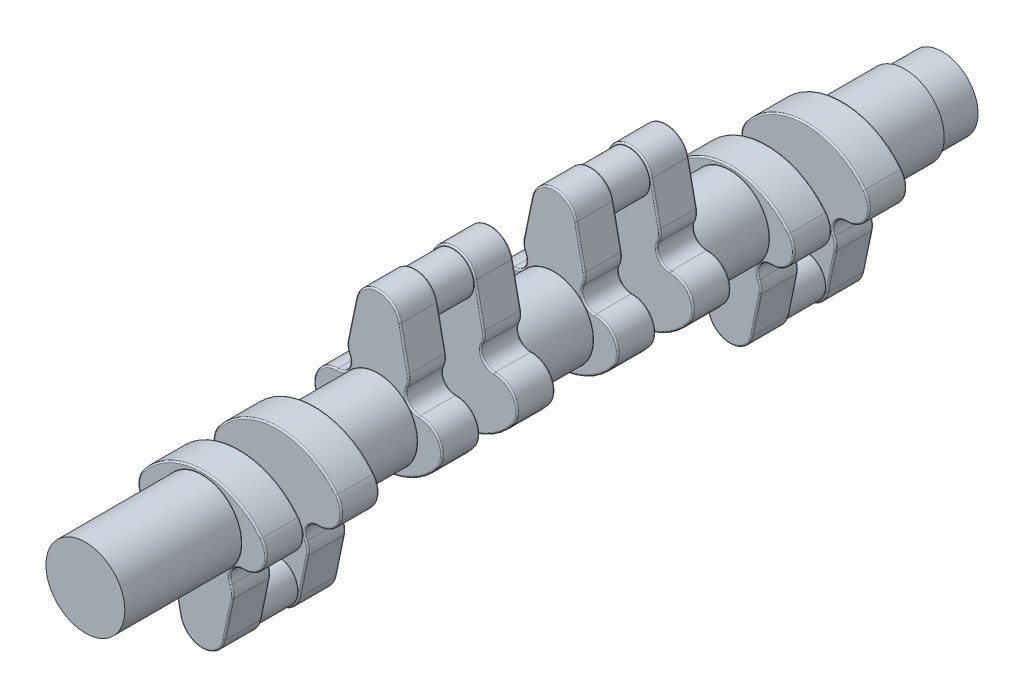
SolidWorks part; units mm, degrees
ref_plane "Front Plane" through (0, 0, 0) normal (0, 0, 1) x (1, 0, 0)
ref_plane "Top Plane" through (0, 0, 0) normal (0, 1, 0) x (1, 0, 0)
ref_plane "Right Plane" through (0, 0, 0) normal (1, 0, 0) x (0, 0, -1)
sketch "Sketch1" plane through (0, 0, 0) normal (0, 0, 1) x (1, 0, 0)
  line L0 (0, 32.598) -> (0, -43.8439) construction
  line L1 (-17.034, 1.0662) -> (-11.7495, -24.3911)
  line L2 (17.034, 1.0662) -> (11.7495, -24.3911)
  arc A0 (31.5175, 32.6781) -> (-31.5175, 32.6781) centre (0, 8.0479) ccw
  arc A1 (-31.5175, 32.6781) -> (-21.8275, 13.2913) centre (-22.0622, 25.289) ccw
  arc A2 (31.5175, 32.6781) -> (21.8275, 13.2913) centre (22.0622, 25.289) cw
  arc A3 (-21.8275, 13.2913) -> (-17.034, 1.0662) centre (-21.6906, 6.2927) cw
  arc A4 (21.8275, 13.2913) -> (17.034, 1.0662) centre (21.6906, 6.2927) ccw
  arc A5 (-11.7495, -24.3911) -> (0, -33.9521) centre (0, -21.9521) ccw
  arc A6 (11.7495, -24.3911) -> (0, -33.9521) centre (0, -21.9521) cw
  point P20 (0, 48.0479)
  dimension "D1" = 40
  dimension "D2" = 12
  dimension "D3" = 7
  dimension "D5" = 12
  dimension "D4" = 26
  dimension "D6" = 82
extrude "Boss-Extrude1" add sketch "Sketch1" along normal blind 20
sketch "Sketch2" plane through (0, 0, 0) normal (0, 0, -1) x (-1, 0, 0)
  line L0 (0, 48.0479) -> (0, -20.6831) construction
  line L1 (34.0622, 25.289) -> (-34.0622, 25.289) construction
  arc A0 (31.5175, 32.6781) -> (-31.5175, 32.6781) centre (0, 8.0479) ccw construction
  arc A1 (21.8275, 13.2913) -> (31.5175, 32.6781) centre (22.0622, 25.289) ccw construction
  arc A2 (-31.5175, 32.6781) -> (-21.8275, 13.2913) centre (-22.0622, 25.289) ccw construction
  circle A3 centre (0, 25.289) radius 21
  dimension "D1" = 42
extrude "Boss-Extrude2" add sketch "Sketch2" along normal blind 16.8
sketch "Sketch3" plane through (0, 0, 20) normal (0, 0, 1) x (1, 0, 0)
  circle A0 centre (0, -21.9521) radius 11
  dimension "D1" = 22
extrude "Boss-Extrude3" add sketch "Sketch3" along normal blind 10
fillet "Fillet1" radius 10 2 edges at (-17.034, 1.0662, 10) (17.034, 1.0662, 10)
fillet "Fillet2" radius 0.8 20 edges at (0, 48.0479, 0) (32.7961, 19.924, 0) (15.8001, 10.0745, 0) (16.3, 0.1337, 0) (13.9576, -13.7539, 0) (0, -33.9521, 0) (-13.9576, -13.7539, 0) (-16.3, 0.1337, 0) (-15.8001, 10.0745, 0) (0, 48.0479, 20) (32.7961, 19.924, 20) (15.8001, 10.0745, 20) (16.3, 0.1337, 20) (13.9576, -13.7539, 20) (0, -33.9521, 20) (-13.9576, -13.7539, 20) (-16.3, 0.1337, 20) (-15.8001, 10.0745, 20) (-32.7961, 19.924, 0) (-32.7961, 19.924, 20)
fillet "Fillet3" radius 0.1 2 edges at (11, -21.9521, 20) (-21, 25.289, 0)
mirror "Mirror1" about plane through (0, -21.9521, 30) normal (0, 0, 1) of bodies 103
sketch "Sketch5" plane through (0, 0, -16.8) normal (0, 0, -1) x (-1, 0, 0)
  circle A0 centre (0, 25.289) radius 21
  dimension "D1" = 42
pattern_linear "LPattern1" count 4 spacing 93.6 along (0, 0, 1) of bodies 104
ref_axis "Axis1" through (0, 25.289, 394.631) along (0, 0, -1)
move or copy body "Body-Move/Copy1" bodies to move or copy 116 115 copy no rotation origin (0, 25.289, 0) rotation axis (0, 0, 1) rotation angle 180
combine bodies "Combine1" operation type add bodies to combine 117 118 119 104
sketch "Sketch10" plane through (0, 0, 0) normal (1, 0, 0) x (0, 0, -1)
  line L0 (-153.7, 38.4597) -> (-153.7, 4.289) construction
  line L1 (-187.1, 38.4597) -> (-187.1, 4.289) construction
  line L2 (-153.7, 38.4597) -> (-153.7, 4.289)
  line L3 (-187.1, 38.4597) -> (-187.1, 4.289)
  dimension "D1" = 33.4
extrude "Boss-Extrude4" add sketch "Sketch5" along normal blind 16.3
sketch "Sketch11" plane through (0, 0, -33.1) normal (0, 0, -1) x (-1, 0, 0)
  circle A0 centre (0, 25.289) radius 19
  dimension "D1" = 38
extrude "Boss-Extrude5" add sketch "Sketch11" along normal blind 20
sketch "Sketch12" plane through (0, 0, 357.6) normal (0, 0, 1) x (1, 0, 0)
  circle A1 centre (0, 25.289) radius 21
  circle A2 centre (0, 25.289) radius 21
  dimension "D1" = 0
extrude "Boss-Extrude6" add sketch "Sketch12" along normal blind 25.3
sketch "Sketch13" plane through (0, 0, 382.9) normal (0, 0, 1) x (1, 0, 0)
  circle A1 centre (0, 25.289) radius 21
  circle A2 centre (0, 25.289) radius 21
  dimension "D1" = 0
extrude "Boss-Extrude7" add sketch "Sketch13" along normal blind 20
